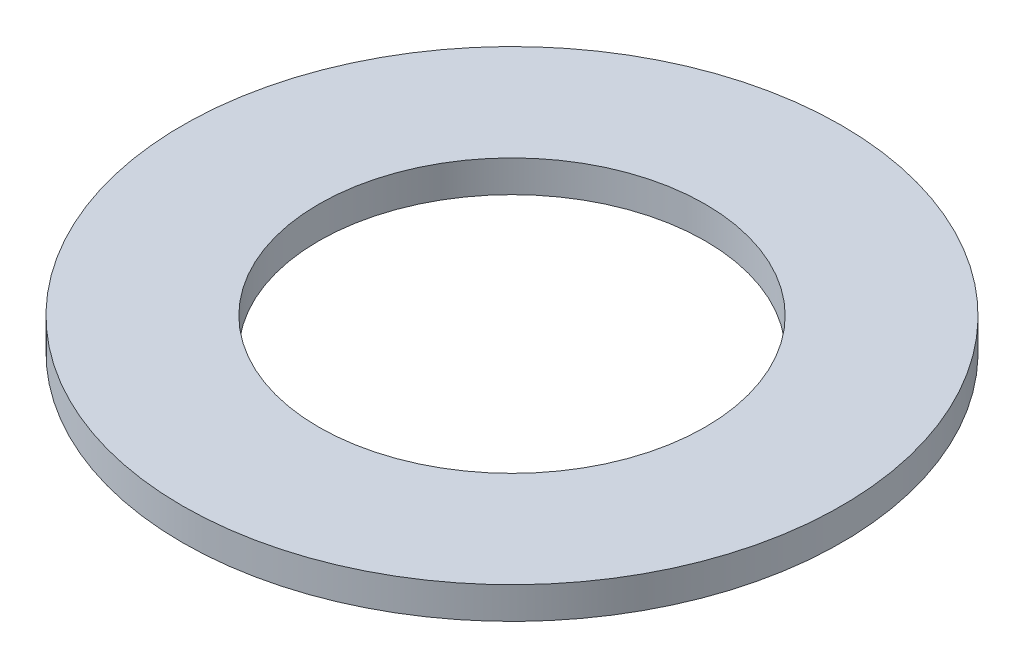
SolidWorks part; units mm, degrees
ref_plane "Front Plane" through (0, 0, 0) normal (0, 0, 1) x (1, 0, 0)
ref_plane "Top Plane" through (0, 0, 0) normal (0, 1, 0) x (1, 0, 0)
ref_plane "Right Plane" through (0, 0, 0) normal (1, 0, 0) x (0, 0, -1)
sketch "Sketch1" plane through (0, 0, 0) normal (0, 1, 0) x (1, 0, 0)
  circle A0 centre (0, 0) radius 72.5
  dimension "FLANGE_OD" = 145
extrude "Boss-Extrude1" add sketch "Sketch1" along normal blind 7
sketch "Sketch2" plane through (0, 0, 0) normal (0, 1, 0) x (1, 0, 0)
  circle A0 centre (0, 0) radius 42.5
  dimension "BORE_D" = 85
extrude "Cut-Extrude1" cut sketch "Sketch2" along normal through all
sketch "Sketch3" plane through (0, 7, 0) normal (0, 1, 0) x (1, 0, 0)
  circle A0 centre (0, 0) radius 32.4433 construction
  circle A1 centre (-32.4433, 0) radius 3.5825
  dimension "BOLT_D" = 7.1649
  dimension "BOLT_PCD" = 64.8865
extrude "Cut-Extrude2" cut sketch "Sketch3" against normal blind 5.2475 rebuild error yes
pattern_circular "CirPattern1" count 6 over 360 rebuild error yes
